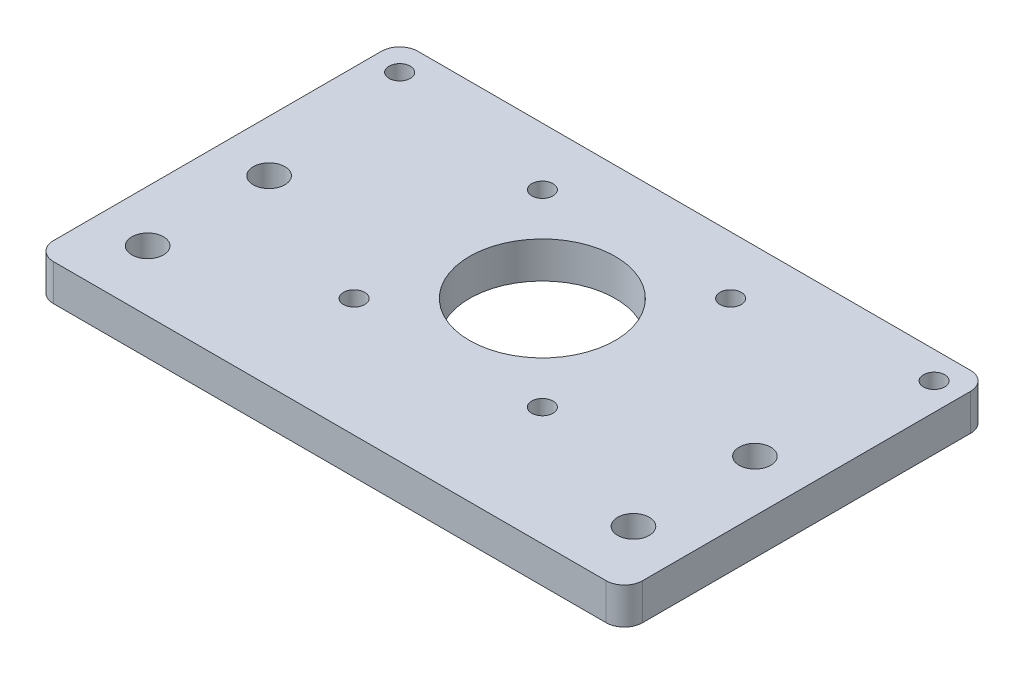
SolidWorks part; units mm, degrees
material "Polycarbonate (PC)"
ref_plane "Front Plane" through (0, 0, 0) normal (0, 0, 1) x (1, 0, 0)
ref_plane "Top Plane" through (0, 0, 0) normal (0, 1, 0) x (1, 0, 0)
ref_plane "Right Plane" through (0, 0, 0) normal (1, 0, 0) x (0, 0, -1)
sketch "Sketch1" plane through (0, 0, 0) normal (0, 1, 0) x (1, 0, 0)
  line L1 (48.5, -30) -> (-48.5, -30)
  line L2 (48.5, -30) -> (48.5, 30)
  line L3 (48.5, 30) -> (-48.5, 30)
  line L4 (-48.5, -30) -> (-48.5, 30)
  line L5 (48.5, -30) -> (-48.5, 30) construction
  line L6 (48.5, 30) -> (-48.5, -30) construction
  point P0 (0, 0)
  dimension "D1" = 97
  dimension "D2" = 60
extrude "Base" add sketch "Sketch1" along normal blind 6
sketch "Sketch2" plane through (0, 6, 0) normal (0, 1, 0) x (1, 0, 0)
  line L1 (0, 5) -> (0, 17.5) construction
  line L2 (-48.5, -30) -> (48.5, -30) construction
  circle A2 centre (0, 5) radius 12
  dimension "D1" = 24
  dimension "D2" = 35
extrude "StepperCaseHole" cut sketch "Sketch2" against normal through all
fillet "FilletEdges3mm" radius 3 4 edges at (48.5, 3, 30) (48.5, 3, -30) (-48.5, 3, -30) (-48.5, 3, 30)
hole_wizard "Ø3.5mm CableTieHoles" positions "Sketch6" profile "Sketch7" hole size "Ø3.5" standard "ISO" end condition through all
sketch "Sketch6" plane through (0, 0, 0) normal (0, -1, 0) x (-1, 0, 0)
  line L0 (-45.5, 30) -> (45.5, 30) construction
  line L1 (-48.5, -27) -> (-48.5, 27) construction
  line L2 (48.5, 27) -> (48.5, -27) construction
  point P0 (-44, 25.5)
  point P2 (44, 25.5)
  dimension "D1" = 4.5
  dimension "D2" = 4.5
  dimension "D3" = 4.5
sketch "Sketch7" plane through (44, 0, -25.5) normal (1, 0, 0) x (0, 0, -1)
  line L0 (0, 0) -> (0, 6)
  line L1 (0, 6) -> (1.75, 6)
  line L2 (1.75, 6) -> (1.75, 0)
  line L5 (1.75, 0) -> (0, 0)
  line L11 (0, -6.35) -> (0, 107.95) construction
  dimension "Thru Hole Dia." = 3.5
  dimension "Thru Hole Depth" = 6
hole_wizard "Ø5.2 (5.2) HolesForCorners" positions "Sketch8" profile "Sketch9" hole size "Ø5.2" standard "ISO" end condition through all
sketch "Sketch8" plane through (0, 6, 0) normal (0, 1, 0) x (1, 0, 0)
  line L0 (0, 0) -> (0, 10.0505) construction
  line L2 (-45.5, -30) -> (45.5, -30) construction
  point P0 (-40, 0)
  point P2 (-40, -20)
  point P4 (40, 0)
  point P6 (40, -20)
  dimension "D1" = 80
  dimension "D2" = 20
  dimension "D3" = 10
sketch "Sketch9" plane through (-40, 6, 0) normal (1, 0, 0) x (0, 0, 1)
  line L0 (0, 0) -> (0, 6)
  line L1 (0, 6) -> (2.6, 6)
  line L2 (2.6, 6) -> (2.6, 0)
  line L5 (2.6, 0) -> (0, 0)
  line L11 (0, -6.35) -> (0, 107.95) construction
  dimension "Thru Hole Dia." = 5.2
  dimension "Thru Hole Depth" = 6
hole_wizard "Ø3.5 (3.5) StepperMountHoles" positions "Sketch10" profile "Sketch11" hole size "Ø3.5" standard "ISO" end condition through all
sketch "Sketch10" plane through (0, 6, 0) normal (0, 1, 0) x (1, 0, 0)
  line L2 (0, 12.5358) -> (0, 5) construction
  line L3 (-45.5, -30) -> (45.5, -30) construction
  point P0 (-15.5, 20.5)
  point P2 (-15.5, -10.5)
  point P4 (15.5, -10.5)
  point P6 (15.5, 20.5)
  point P20 (-126.0094, 14.1745)
  dimension "D1" = 31
  dimension "D2" = 31
  dimension "D3" = 19.5
sketch "Sketch11" plane through (-15.5, 6, -20.5) normal (1, 0, 0) x (0, 0, 1)
  line L0 (0, 0) -> (0, 6)
  line L1 (0, 6) -> (1.75, 6)
  line L2 (1.75, 6) -> (1.75, 0)
  line L5 (1.75, 0) -> (0, 0)
  line L11 (0, -6.35) -> (0, 107.95) construction
  dimension "Thru Hole Dia." = 3.5
  dimension "Thru Hole Depth" = 6
